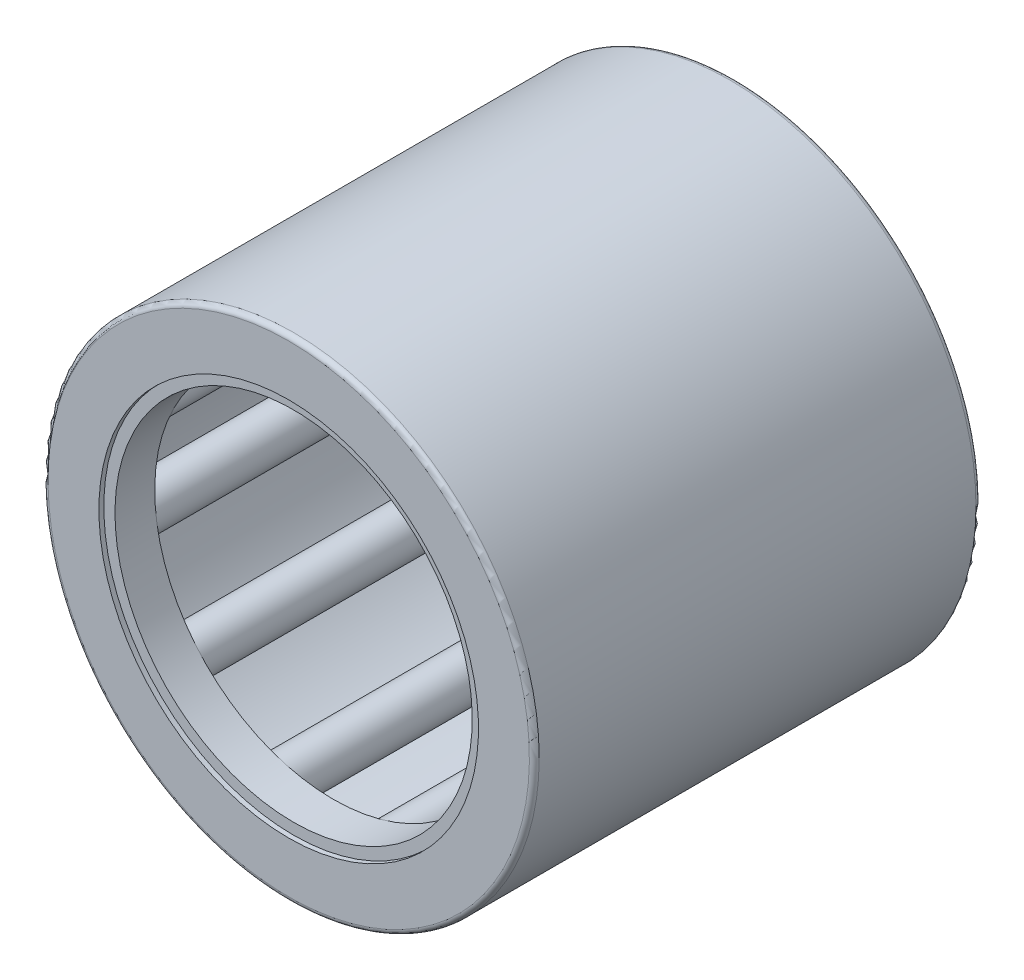
SolidWorks part; units mm, degrees
material "Plain Carbon Steel"
ref_plane "Front Plane" through (0, 0, 0) normal (0, 0, 1) x (1, 0, 0)
ref_plane "Top Plane" through (0, 0, 0) normal (0, 1, 0) x (1, 0, 0)
ref_plane "Right Plane" through (0, 0, 0) normal (1, 0, 0) x (0, 0, -1)
sketch "Sketch1" plane through (0, 0, 0) normal (1, 0, 0) x (0, 0, -1)
  line L0 (-7.9375, 0) -> (7.9375, 0) construction
  line L1 (0, 0) -> (0, 8.7312) construction
  line L2 (-7.9375, 0) -> (-7.9375, 8.7312) construction
  line L3 (-7.9375, 8.7312) -> (7.9375, 8.7312)
  line L4 (7.9375, 8.7312) -> (7.9375, 0) construction
  line L5 (7.9375, 0) -> (7.1438, 0) construction
  line L6 (7.1438, 0) -> (7.1438, 7.9375) construction
  line L7 (7.1438, 7.9375) -> (-7.1438, 7.9375)
  line L8 (-7.1438, 7.9375) -> (-7.1438, 0) construction
  line L9 (-7.1438, 0) -> (-7.9375, 0) construction
  line L10 (-7.9375, 8.7312) -> (-7.9375, 6.7469)
  line L11 (-7.9375, 6.7469) -> (-7.1438, 6.7469)
  line L12 (-7.1438, 6.7469) -> (-7.1438, 7.9375)
  line L13 (7.1438, 8.7312) -> (7.1438, 7.9375) construction
  line L14 (7.1438, 7.9375) -> (7.1438, 6.7469)
  line L15 (7.1438, 6.7469) -> (7.9375, 6.7469)
  line L16 (7.9375, 6.7469) -> (7.9375, 8.7312)
  line L17 (7.1438, 7.9375) -> (7.1438, 7.1437) construction
  line L18 (7.1438, 7.1437) -> (7.1438, 6.35) construction
  point P5 (0, 6.35)
  dimension "Width" = 15.875
  dimension "OD" = 17.4625
  dimension "Shaft Dia" = 12.7
revolve "Revolve1" add sketch "Sketch1" angle 360 about L0
sketch "Sketch2" plane through (0, 0, 0) normal (1, 0, 0) x (0, 0, -1)
  line L0 (7.1438, 7.9375) -> (-7.1438, 7.9375) construction
  line L1 (-6.35, 7.1437) -> (6.35, 7.1437) construction
  line L2 (-6.35, 7.1437) -> (-6.35, 7.9375) construction
  line L3 (-6.35, 7.9375) -> (6.35, 7.9375)
  line L4 (6.35, 7.1437) -> (6.35, 7.9375) construction
  line L5 (7.1438, 6.7469) -> (7.9375, 6.7469) construction
  line L6 (-7.1438, 7.1437) -> (-6.35, 7.1437) construction
  line L7 (6.35, 7.1437) -> (7.1438, 7.1437) construction
  line L8 (-7.9375, 6.7469) -> (-7.1438, 6.7469) construction
  line L9 (-6.35, 7.3422) -> (-6.35, 6.9453) construction
  line L10 (-7.1438, 7.1437) -> (-7.1438, 6.7469) construction
  line L11 (-6.35, 7.9375) -> (-6.35, 7.3422)
  line L12 (6.35, 7.9375) -> (6.35, 7.3422)
  line L13 (6.35, 7.3422) -> (-6.35, 7.3422)
  line L14 (0, 7.9375) -> (0, 6.35) construction
  line L15 (-7.1438, 6.7469) -> (-7.1438, 7.9375) construction
  line L16 (-6.35, 6.9453) -> (-7.1438, 6.9453) construction
  line L17 (0, 0) -> (7.9375, 0) construction
  line L31 (7.9375, -8.7313) -> (7.9375, 8.7312) construction
  point P16 (0, 7.1437)
revolve "Revolve2" add sketch "Sketch2" angle 360 about L1
sketch "Sketch3" plane through (0, 0, 0) normal (1, 0, 0) x (0, 0, -1)
  line L0 (7.1438, 7.9375) -> (7.1438, 6.7469) construction
  line L1 (-7.1438, 7.1437) -> (7.1438, 7.1437)
  line L2 (-7.1438, 7.1437) -> (-7.1438, 7.3422)
  line L3 (-7.1438, 7.3422) -> (7.1438, 7.3422)
  line L4 (7.1438, 7.1437) -> (7.1438, 7.3422)
  line L5 (0, 0) -> (7.9375, 0) construction
  line L6 (7.9375, -8.7313) -> (7.9375, 8.7312) construction
revolve "Revolve3" add sketch "Sketch3" angle 360 about L1
ref_axis "Axis1" through (0, 0, -7.9375) along (0, 0, 1)
pattern_circular "CirPattern1" count 11 every 32.727 about axis through (0, 0, -7.9375) along (0, 0, 1) of bodies 166 167
fillet "Fillet1" radius 0.1746 2 edges at (0, -8.7313, -7.9375) (0, -8.7313, 7.9375)
sketch "Sketch4" plane through (0, 0, 0) normal (1, 0, 0) x (0, 0, -1)
  line L1 (7.7629, 6.35) -> (6.35, 6.35)
  line L2 (7.7629, 6.35) -> (7.7629, 6.7469)
  line L3 (7.7629, 6.7469) -> (6.35, 6.7469)
  line L4 (6.35, 6.35) -> (6.35, 6.7469)
  line L5 (-7.9375, 6.7469) -> (-7.1438, 6.7469) construction
  line L6 (7.7629, -8.7313) -> (7.7629, 8.7312) construction
  line L7 (6.35, 7.9375) -> (6.35, 7.3422) construction
revolve "Revolve4" add sketch "Sketch4" angle 360 about L0
sketch "Sketch5" plane through (0, 0, 0) normal (1, 0, 0) x (0, 0, -1)
  line L0 (-7.7629, 8.7312) -> (-7.7629, -8.7313) construction
  line L1 (-6.35, 6.35) -> (-7.7629, 6.35)
  line L2 (-6.35, 6.35) -> (-6.35, 6.7469)
  line L3 (-6.35, 6.7469) -> (-7.7629, 6.7469)
  line L4 (-7.7629, 6.35) -> (-7.7629, 6.7469)
  line L6 (-6.35, 7.9375) -> (-6.35, 7.3422) construction
  line L7 (-7.9375, 6.7469) -> (-7.1438, 6.7469) construction
revolve "Revolve5" add sketch "Sketch5" angle 360 about L0
sketch "Front View" plane through (0, 0, 0) normal (0, 0, 1) x (1, 0, 0)
  circle A0 centre (0, 0) radius 6.35 construction
  circle A1 centre (0, 0) radius 8.7312 construction
  dimension "OD" = 17.4625
  dimension "ID" = 12.7
sketch "Right View" plane through (0, 0, 0) normal (1, 0, 0) x (0, 0, -1)
  line L0 (-7.9375, 8.7312) -> (7.9375, 8.7312) construction
  dimension "Width" = 15.875
ref_axis "Center Axis 1" through (0, 0, -7.7629) along (0, 0, 1)
ref_plane "Contact Plane 1" through (0, 0, 7.9375) normal (0, 0, 1) x (1, 0, 0)
ref_plane "Contact Plane 2" through (0, 0, -7.9375) normal (0, 0, -1) x (-1, 0, 0)
equation "\"Rollers@CirPattern1\" = \"OD@Sketch1\"*16"
equation "\"D1@Fillet1\" = \"OD@Sketch1\"*.01"
equation "\"Angle@CirPattern1\"= 360 / \"Rollers@CirPattern1\""
equation "\"OD@Front View\"=\"OD@Sketch1\""
equation "\"ID@Front View\"=\"Shaft Dia@Sketch1\""
equation "\"Width@Right View\"=\"Width@Sketch1\""
